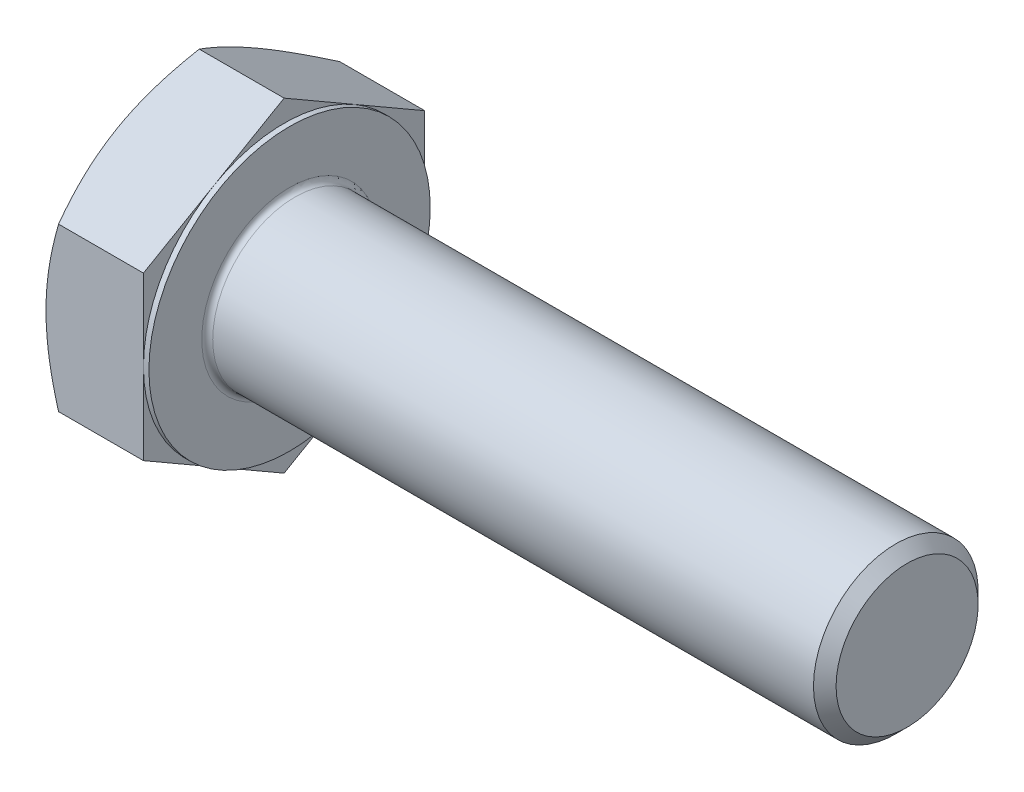
SolidWorks part; units mm, degrees
ref_plane "Front Plane" through (0, 0, 0) normal (0, 0, 1) x (1, 0, 0)
ref_plane "Top Plane" through (0, 0, 0) normal (0, 1, 0) x (1, 0, 0)
ref_plane "Right Plane" through (0, 0, 0) normal (1, 0, 0) x (0, 0, -1)
sketch "BaseHeadSke" plane through (0, 0, 0) normal (1, 0, 0) x (0, 0, -1)
  line L1 (20.5, 11.8357) -> (0, 23.6714)
  line L2 (0, 23.6714) -> (-20.5, 11.8357)
  line L3 (-20.5, 11.8357) -> (-20.5, -11.8357)
  line L4 (-20.5, -11.8357) -> (0, -23.6714)
  line L5 (0, -23.6714) -> (20.5, -11.8357)
  line L6 (20.5, -11.8357) -> (20.5, 11.8357)
  circle A0 centre (0, 0) radius 20.5 construction
extrude "BaseHead" add sketch "BaseHeadSke" along normal blind 15
sketch "BodySke" plane through (0, 0, 0) normal (0, 0, 1) x (1, 0, 0)
  line L0 (0, 0) -> (105, 0)
  line L1 (105, 0) -> (105, 10.352)
  line L2 (105, 10.352) -> (103.352, 12)
  line L3 (103.352, 12) -> (0, 12)
  line L4 (0, 12) -> (0, 0)
  line L5 (15, 11.8357) -> (15, -11.8357) construction
  line L6 (0, 0) -> (159.3976, 0) construction
  line L7 (51, -84.3176) -> (51, 77.7215) construction
  line L8 (102, -21.5941) -> (102, 39.2994) construction
  dimension "Thread_length" = 54
  dimension "Advance" = 3
revolve "BaseBody" add sketch "BodySke" angle 360 about L6
cosmetic thread "ThreadCosmetic" [suppressed] parameters "Thread_length"=54, "Thread_minor"=20.704
sketch "HeadChamferSke" plane through (0, 0, 0) normal (0, 0, 1) x (1, 0, 0)
  line L0 (1.831, 23.6714) -> (0, 23.6714)
  line L1 (0, 23.6714) -> (0, 20.5)
  line L2 (0, 20.5) -> (1.831, 23.6714)
  line L3 (0, 0) -> (120.9185, 0) construction
  dimension "D1" = 30
revolve "HeadChamfer" cut sketch "HeadChamferSke" angle 360 about L3
sketch "BearingFaceSke" plane through (0, 0, 0) normal (0, 0, 1) x (1, 0, 0)
  line L0 (0, 0) -> (129.6443, 0) construction
  line L1 (14.2, 23.6714) -> (15, 23.6714)
  line L2 (14.2, 23.6714) -> (14.2, 20.5)
  line L3 (14.2, 20.5) -> (15, 20.5)
  line L4 (15, 23.6714) -> (15, 20.5)
  dimension "Bearing_height" = 0.8
  dimension "Dw" = 41
revolve "BearingFace" cut sketch "BearingFaceSke" angle 360 about L0
fillet "Fillet" radius 0.8 1 edges at (15, 0, -12)
sketch "ThdSchSke" plane through (0, 0, 0) normal (0, 0, 1) x (1, 0, 0)
  line L0 (101.0485, 13.9029) -> (101.0485, 12)
  line L1 (101.0485, 12) -> (102, 10.352)
  line L2 (102, 10.352) -> (102.9515, 12)
  line L3 (102.9515, 12) -> (102.9515, 13.9029)
  line L4 (102.9515, 13.9029) -> (101.0485, 13.9029)
  line L6 (0, 0) -> (141.9934, 0) construction
  line L7 (105, -10.352) -> (105, 10.352) construction
  dimension "D2" = 20.704
  dimension "D3" = 24
  dimension "Advance" = 3
revolve "ThreadSchematic" [suppressed] cut sketch "ThdSchSke" angle 360 about L6
pattern_linear "ThdSchPat" [suppressed] count 17 spacing 3 along (-1, 0, 0) of bodies 107
equation "\"Thread_minor@ThreadCosmetic\" = \"Minor_dia@BodySke\""
equation "\"Thread_length@ThreadCosmetic\" = \"Thread_length@BodySke\""
equation "\"Head_chamfer@HeadChamferSke\" = \"Width_flats@BaseHeadSke\""
equation "\"D2@ThdSchSke\" = \"Minor_dia@BodySke\""
equation "\"D3@ThdSchSke\" = \"Diameter@BodySke\""
equation "\"Advance@ThdSchSke\" = \"Advance@BodySke\""
equation "\"D3@ThdSchPat\" = \"Advance@BodySke\""
equation "\"D1@ThdSchPat\" =  int( \"Thread_length@BodySke\"/\"Advance@BodySke\" )-1"
